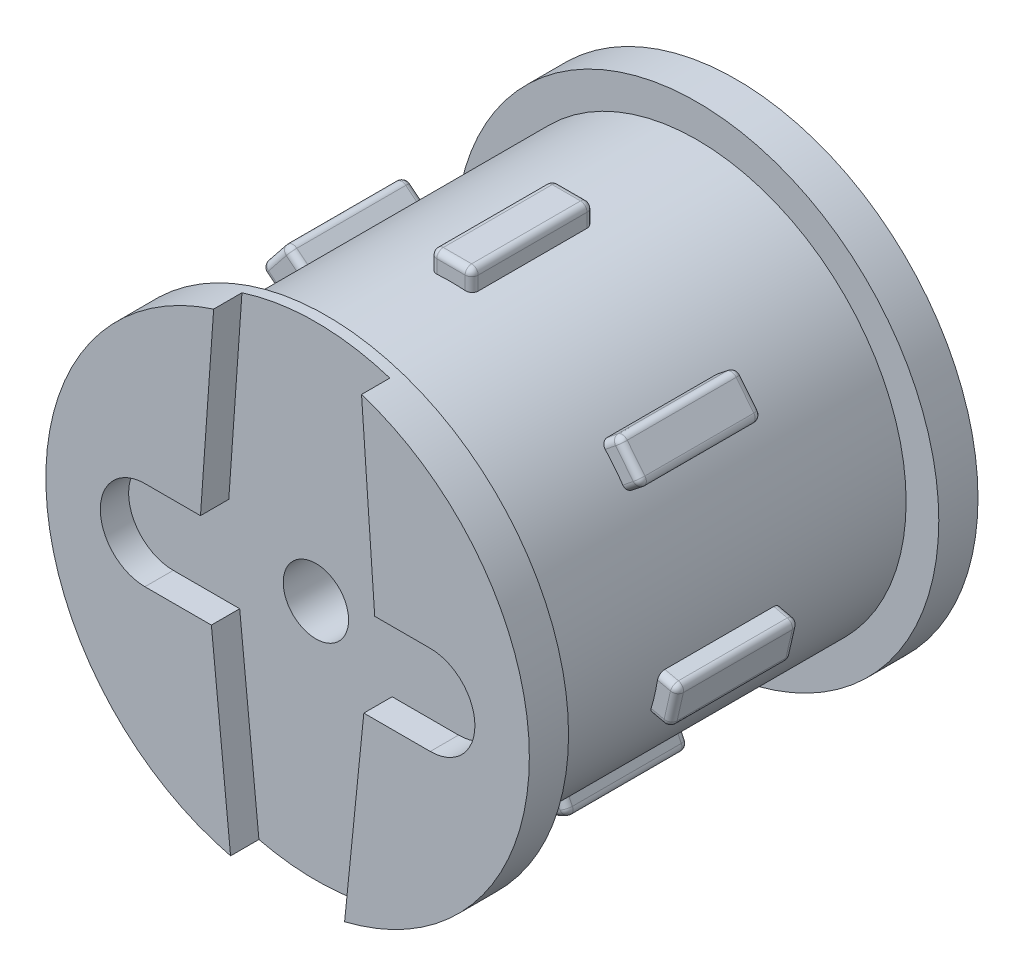
SolidWorks part; units mm, degrees
ref_plane "Ebene vorne" through (0, 0, 0) normal (0, 0, 1) x (1, 0, 0)
ref_plane "Ebene oben" through (0, 0, 0) normal (0, 1, 0) x (1, 0, 0)
ref_plane "Ebene rechts" through (0, 0, 0) normal (1, 0, 0) x (0, 0, -1)
sketch "Skizze1" plane through (0, 0, 0) normal (0, 0, 1) x (1, 0, 0)
  circle A0 centre (0, 0) radius 9.6
  dimension "D1" = 19.2
extrude "Aufsatz-Linear austragen1" add sketch "Skizze1" along normal blind 10.3 and the other way blind 10.3
ref_axis "Rotationsachse" through (0, 0, -10.3) along (0, 0, 1)
sketch "Skizze2" plane through (0, 0, 10.3) normal (0, 0, 1) x (1, 0, 0)
  circle A0 centre (0, 0) radius 11.1
  dimension "D1" = 22.2
extrude "Aufsatz-Linear austragen2" add sketch "Skizze2" against normal blind 1.8
sketch "Skizze3" plane through (0, 0, -10.3) normal (0, 0, -1) x (-1, 0, 0)
  circle A0 centre (0, 0) radius 11.1
  dimension "D1" = 22.2
extrude "Aufsatz-Linear austragen3" add sketch "Skizze3" against normal blind 1.8
sketch "Skizze12" plane through (0, 0, 10.3) normal (0, 0, 1) x (1, 0, 0)
  line L0 (1.9899, -17.001) -> (3.5, -2.05)
  line L1 (-3.05, 2.05) -> (3.05, 2.05)
  line L2 (-3.05, 2.05) -> (-3.05, -2.05)
  line L3 (-3.05, -2.05) -> (3.05, -2.05)
  line L4 (3.05, 2.05) -> (3.05, -2.05)
  line L5 (-3.05, 2.05) -> (3.05, -2.05) construction
  line L6 (-3.05, -2.05) -> (3.05, 2.05) construction
  line L7 (3.05, 2.05) -> (6.55, 2.05)
  line L8 (3.05, 2.05) -> (3.05, -2.05)
  line L9 (3.05, -2.05) -> (6.55, -2.05)
  line L10 (6.55, 2.05) -> (6.55, -2.05)
  line L11 (-3.05, -2.05) -> (-3.5, -2.05)
  line L12 (-1.9899, -17.001) -> (-3.5, -2.05)
  line L13 (4, 2.05) -> (2.7431, 19.7448)
  line L14 (-4, 2.05) -> (-2.7431, 19.7448)
  line L16 (-3.05, -2.05) -> (-6.55, -2.05)
  line L17 (-3.05, -2.05) -> (-3.05, 2.05)
  line L18 (-3.05, 2.05) -> (-6.55, 2.05)
  line L19 (-6.55, -2.05) -> (-6.55, 2.05)
  circle A0 centre (6.55, 0) radius 2.05
  circle A1 centre (0, -16.8) radius 2
  circle A2 centre (0, 19.55) radius 2.75
  circle A3 centre (-6.55, 0) radius 2.05
  point P0 (0, 0)
  point P12 (0, -2.05)
  circle M11 centre (0, 0) radius 11.1
  dimension "D5" = 4
  dimension "D9" = 17.5
  dimension "D13" = 5.5
  dimension "D6" = 4.1
  dimension "D2" = 4.1
  dimension "D1" = 6.1
  dimension "D3" = 3.5
  dimension "D4" = 14.75
  dimension "D7" = 3.5
  dimension "D8" = 3.5
  dimension "D10" = 4
  dimension "D11" = 4
  dimension "D12" = 3.5
extrude "Schnitt-Linear austragen1" cut sketch "Skizze12" against normal blind 1.3 contours A1 M11 | L11 L9 L3 M11 | L4 L1 L2 L3 | A0 L7 L4 L9 | L10 A0 | L10 A0 | L18 L1 L7 L13 L14 M11 | A2 L14 L13 M11 | L17 L16 L19 L18 | A3 | A2 | L2 L1 L4 L3 region at (0, -13.1061, 10.3) region at (0, -6.3029, 10.3) region at (4.0504, 0, 10.3) region at (0, 0, 10.3) region at (5.68, 0, 10.3) region at (7.42, 0, 10.3) region at (0, 6.3626, 10.3) region at (0, 14.1384, 10.3)
sketch "Skizze8" plane through (0, 0, 0) normal (1, 0, 0) x (0, 0, -1)
  line L0 (10.3, 0) -> (10.3, 8)
  line L1 (10.3, -11.1) -> (10.3, 11.1) construction
  line L2 (10.3, 8) -> (8.5, 8)
  line L3 (8.5, 11.1) -> (8.5, -11.1) construction
  line L4 (8.5, 8) -> (-6.7, 6)
  line L6 (-6.7, 6) -> (-6.7, 0)
  line L7 (-6.7, 0) -> (10.3, 0)
  dimension "D1" = 8
  dimension "D2" = 6
  dimension "D3" = 17
revolve "Schnitt-Rotation1" cut sketch "Skizze8" angle 360 about axis through (0, 0, -10.3) along (0, 0, 1)
ref_plane "Schnittebene_Zaehne" through (0, 0, 0) normal (0, 0, -1) x (-1, 0, 0)
sketch "Skizze11" plane through (0, 0, 0) normal (0, 0, -1) x (-1, 0, 0)
  line L0 (0, 0) -> (0, 12.664) construction
  line L6 (-0.95, 8.71) -> (0.95, 8.71)
  line L7 (-0.95, 8.71) -> (-0.95, 10.49)
  line L8 (-0.95, 10.49) -> (0.95, 10.49)
  line L9 (0.95, 8.71) -> (0.95, 10.49)
  line L10 (-0.95, 8.71) -> (0.95, 10.49) construction
  line L11 (-0.95, 10.49) -> (0.95, 8.71) construction
  circle A1 centre (0, 0) radius 9.6 construction
  point P3 (0, 9.6)
  dimension "D1" = 0.89
  dimension "D2" = 1.9
extrude "Aufsatz-Linear austragen4" add sketch "Skizze11" along normal blind 2.8 and the other way blind 2.8
pattern_circular "Kreismuster2" count 7 over 360 about axis through (0, 0, -10.3) along (0, 0, 1) of "Aufsatz-Linear austragen4"
fillet "Verrundung1" radius 0.3 56 edges at (8.2014, 6.5404, 2.8) (7.6091, 7.2831, 0) (8.2014, 6.5404, -2.8) (8.7937, 5.7977, 0) (-8.4274, 5.5055, 2.8) (-7.2428, 6.991, 2.8) (-7.2428, 6.991, -2.8) (-8.4274, 5.5055, -2.8) (-9.5588, -3.1562, -2.8) (-9.9816, -1.3038, -2.8) (-9.5588, -3.1562, 2.8) (-9.9816, -1.3038, 2.8) (-5.2041, -8.6168, -2.8) (-3.4922, -9.4412, -2.8) (-3.4922, -9.4412, 2.8) (-5.2041, -8.6168, 2.8) (5.2041, -8.6168, 2.8) (3.4922, -9.4412, 2.8) (3.4922, -9.4412, -2.8) (5.2041, -8.6168, -2.8) (9.5588, -3.1562, 2.8) (9.5588, -3.1562, -2.8) (9.9816, -1.3038, 2.8) (9.9816, -1.3038, -2.8) (8.4274, 5.5055, 2.8) (8.4274, 5.5055, -2.8) (7.2428, 6.991, -2.8) (7.2428, 6.991, 2.8) (0.95, 10.0214, 2.8) (0.95, 10.0214, -2.8) (-0.95, 10.0214, -2.8) (-0.95, 10.0214, 2.8) (10.4384, -1.4081, 0) (10.227, -2.3342, 2.8) (10.227, -2.3342, -2.8) (10.0156, -3.2604, 0) (4.5514, -9.4512, 2.8) (4.5514, -9.4512, -2.8) (5.4074, -9.039, 0) (3.6955, -9.8634, 0) (-4.5514, -9.4512, 2.8) (-4.5514, -9.4512, -2.8) (-5.4074, -9.039, 0) (-3.6955, -9.8634, 0) (-10.227, -2.3342, 2.8) (-10.227, -2.3342, -2.8) (-10.0156, -3.2604, 0) (-10.4384, -1.4081, 0) (-8.2014, 6.5404, -2.8) (-8.2014, 6.5404, 2.8) (-8.7937, 5.7977, 0) (-7.6091, 7.2831, 0) (0, 10.49, -2.8) (0, 10.49, 2.8) (0.95, 10.49, 0) (-0.95, 10.49, 0)
sketch "Skizze14" plane through (0, 0, 10.3) normal (0, 0, 1) x (1, 0, 0)
  circle A0 centre (0, 0) radius 1.5
  dimension "D1" = 3
extrude "Schnitt-Linear austragen2" cut sketch "Skizze14" against normal up to surface (3.6 mm away) up to face at (-6, 0, 6.7)
